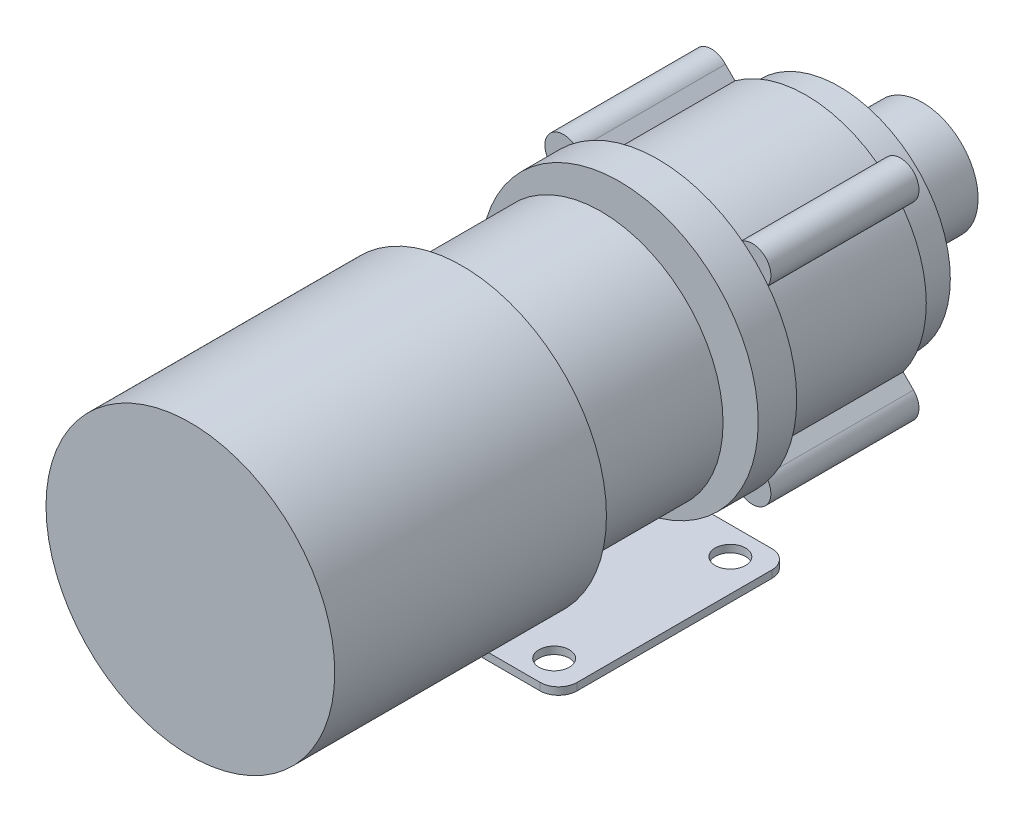
SolidWorks part; units mm, degrees
ref_plane "Front Plane" through (0, 0, 0) normal (0, 0, 1) x (1, 0, 0)
ref_plane "Top Plane" through (0, 0, 0) normal (0, 1, 0) x (1, 0, 0)
ref_plane "Right Plane" through (0, 0, 0) normal (1, 0, 0) x (0, 0, -1)
sketch "Sketch1" plane through (0, 0, 0) normal (0, 1, 0) x (1, 0, 0)
  line L0 (0, 0) -> (0, -251.206)
  line L1 (0, -251.206) -> (49.53, -251.206)
  line L2 (49.53, -251.206) -> (49.53, -157.988)
  line L3 (49.53, -157.988) -> (41.91, -157.988)
  line L4 (41.91, -157.988) -> (41.91, -110.363)
  line L5 (41.91, -110.363) -> (12.7, -110.363)
  line L6 (12.7, -110.363) -> (12.7, -104.013)
  line L7 (12.7, -104.013) -> (47.625, -104.013)
  line L8 (47.625, -104.013) -> (47.625, -90.805)
  line L9 (47.625, -90.805) -> (41.275, -90.805)
  line L10 (41.275, -90.805) -> (41.275, -40.005)
  line L11 (41.275, -40.005) -> (38.1, -40.005)
  line L12 (38.1, -40.005) -> (38.1, -28.575)
  line L13 (38.1, -28.575) -> (19.05, -28.575)
  line L14 (19.05, -28.575) -> (19.05, 0)
  line L15 (19.05, 0) -> (0, 0)
  point P15 (0, 0)
  point P19 (0, 0)
  point P20 (1.1967, 0)
  dimension "D1" = 93.218
  dimension "D2" = 47.625
  dimension "D3" = 6.35
  dimension "D4" = 13.208
  dimension "D5" = 50.8
  dimension "D6" = 11.43
  dimension "D7" = 28.575
  dimension "D8" = 49.53
  dimension "D9" = 41.91
  dimension "D10" = 12.7
  dimension "D11" = 47.625
  dimension "D12" = 41.275
  dimension "D13" = 38.1
  dimension "D14" = 19.05
revolve "Revolve1" add sketch "Sketch1" angle 360 about L0
sketch "Sketch2" plane through (0, 0, 40.005) normal (0, 0, -1) x (-1, 0, 0)
  line L0 (-27.9286, 36.9089) -> (-23.4385, 32.4187) construction
  line L1 (-24.3482, 33.3285) -> (-27.9286, 36.9089)
  line L2 (33.3285, 24.3482) -> (36.9089, 27.9286)
  line L3 (-32.4187, 32.4187) -> (-23.4385, 32.4187) construction
  line L4 (27.6284, 36.5871) -> (24.3482, 33.3285)
  line L5 (36.9089, 27.9286) -> (32.4187, 23.4385) construction
  line L6 (-32.4187, 32.4187) -> (-29.1858, 29.1858) construction
  line L7 (-36.9089, 27.9286) -> (-32.4187, 23.4385) construction
  line L8 (32.4187, 32.4187) -> (32.4187, 23.4385) construction
  line L9 (32.4187, 32.4187) -> (29.1858, 29.1858) construction
  line L10 (27.9286, 36.9089) -> (23.4385, 32.4187) construction
  line L11 (-36.5871, 27.6284) -> (-33.3285, 24.3482)
  line L12 (23.4385, 32.4187) -> (32.4187, 32.4187) construction
  line L13 (24.3482, -33.3285) -> (27.9286, -36.9089)
  line L14 (36.5871, -27.6284) -> (33.3285, -24.3482)
  line L15 (27.9286, -36.9089) -> (23.4385, -32.4187) construction
  line L16 (32.4187, -32.4187) -> (23.4385, -32.4187) construction
  line L17 (32.4187, -32.4187) -> (29.1858, -29.1858) construction
  line L18 (36.9089, -27.9286) -> (32.4187, -23.4385) construction
  line L19 (32.4187, -23.4385) -> (32.4187, -32.4187) construction
  line L20 (-33.3285, -24.3482) -> (-36.9089, -27.9286)
  line L21 (-32.4187, 23.4385) -> (-32.4187, 32.4187) construction
  line L22 (-27.6284, -36.5871) -> (-24.3482, -33.3285)
  line L23 (-36.9089, -27.9286) -> (-32.4187, -23.4385) construction
  line L24 (-32.4187, -32.4187) -> (-32.4187, -23.4385) construction
  line L25 (-32.4187, -32.4187) -> (-29.1858, -29.1858) construction
  line L26 (-27.9286, -36.9089) -> (-23.4385, -32.4187) construction
  line L27 (-23.4385, -32.4187) -> (-32.4187, -32.4187) construction
  arc A0 (-27.6161, 36.5964) -> (-36.5964, 27.6161) centre (0, 0) ccw construction
  arc A1 (-27.9286, 36.9089) -> (-36.5871, 27.6284) centre (-32.4187, 32.4187) ccw
  circle A2 centre (0, 0) radius 38.1 construction
  arc A3 (36.9089, 27.9286) -> (27.6284, 36.5871) centre (32.4187, 32.4187) ccw
  arc A4 (33.3285, 24.3482) -> (24.3482, 33.3285) centre (0, 0) ccw
  arc A5 (-24.3482, 33.3285) -> (-33.3285, 24.3482) centre (0, 0) ccw
  arc A6 (36.5964, 27.6161) -> (27.6161, 36.5964) centre (0, 0) ccw construction
  arc A7 (27.9286, -36.9089) -> (36.5871, -27.6284) centre (32.4187, -32.4187) ccw
  arc A8 (24.3482, -33.3285) -> (33.3285, -24.3482) centre (0, 0) ccw
  arc A9 (27.6161, -36.5964) -> (36.5964, -27.6161) centre (0, 0) ccw construction
  arc A10 (-36.9089, -27.9286) -> (-27.6284, -36.5871) centre (-32.4187, -32.4187) ccw
  arc A11 (-33.3285, -24.3482) -> (-24.3482, -33.3285) centre (0, 0) ccw
  arc A12 (-36.5964, -27.6161) -> (-27.6161, -36.5964) centre (0, 0) ccw construction
  point P50 (0, 0)
  dimension "D1" = 45.847
  dimension "D2" = 12.7
  dimension "D3" = 41.275
  dimension "D4" = 4
extrude "Boss-Extrude1" add sketch "Sketch2" against normal blind 50.8 separate body
ref_plane "Plane2" [suppressed] through (0, 0, 133.35) normal (0, 0, 1) x (1, 0, 0)
sketch "Sketch3" [suppressed] plane through (0, 0, 251.206) normal (0, 0, 1) x (1, 0, 0)
  line L0 (0, 0) -> (-14.9938, -25.97)
  line L1 (0, 0) -> (14.9938, -25.97)
  line L2 (0, 0) -> (0, -29.9876) construction
  line L3 (2.8571, 2.4086) -> (-13.8805, -26.5817)
  line L4 (13.8805, -26.5817) -> (-3.5159, 3.5497)
  circle A0 centre (0, 0) radius 29.9876
  circle A1 centre (0, 0) radius 28.7176
  dimension "D1" = 1.27
  dimension "D5" = 1.27
  dimension "D2" = 30
  dimension "D3" = 30
  dimension "D6" = 1.27
ref_plane "Plane3" through (0, -49.53, 0) normal (0, -1, 0) x (-1, 0, 0)
sketch "Sketch4" plane through (0, -49.53, 0) normal (0, -1, 0) x (-1, 0, 0)
  line L0 (0, -157.988) -> (0, -251.206) construction
  line L1 (49.53, -157.988) -> (-49.53, -157.988) construction
  line L2 (-49.53, -251.206) -> (49.53, -251.206) construction
  line L4 (-38.1, -169.3256) -> (38.1, -169.3256)
  line L5 (-44.45, -162.9756) -> (-44.45, -96.1736)
  line L6 (-38.1, -89.8236) -> (38.1, -89.8236)
  line L7 (44.45, -162.9756) -> (44.45, -96.1736)
  line L8 (-44.45, -169.3256) -> (44.45, -89.8236) construction
  line L9 (-44.45, -89.8236) -> (44.45, -169.3256) construction
  arc A0 (38.1, -169.3256) -> (44.45, -162.9756) centre (38.1, -162.9756) ccw
  arc A1 (-38.1, -169.3256) -> (-44.45, -162.9756) centre (-38.1, -162.9756) cw
  arc A2 (-44.45, -96.1736) -> (-38.1, -89.8236) centre (-38.1, -96.1736) cw
  arc A3 (38.1, -89.8236) -> (44.45, -96.1736) centre (38.1, -96.1736) cw
  point P6 (0, -129.5746)
  point P11 (0, -129.5746)
  dimension "D3" = 6.35
  dimension "D1" = 79.502
  dimension "D2" = 88.9
extrude "Boss-Extrude2" add sketch "Sketch4" along normal blind 2.54 separate body
sketch "Sketch5" plane through (0, -52.07, 0) normal (0, -1, 0) x (1, 0, 0)
  line L0 (44.45, 129.5746) -> (-44.45, 129.5746) construction
  line L1 (44.45, 96.1736) -> (44.45, 162.9756) construction
  line L2 (-44.45, 162.9756) -> (-44.45, 96.1736) construction
  line L4 (33.401, 159.8006) -> (-33.401, 159.8006) construction
  line L5 (33.401, 159.8006) -> (33.401, 99.3486) construction
  line L6 (33.401, 99.3486) -> (-33.401, 99.3486) construction
  line L7 (-33.401, 159.8006) -> (-33.401, 99.3486) construction
  line L8 (33.401, 159.8006) -> (-33.401, 99.3486) construction
  line L9 (33.401, 99.3486) -> (-33.401, 159.8006) construction
  circle A0 centre (33.401, 159.8006) radius 5.207
  circle A1 centre (33.401, 99.3486) radius 5.207
  circle A2 centre (-33.401, 159.8006) radius 5.207
  circle A3 centre (-33.401, 99.3486) radius 5.207
  point P6 (0, 129.5746)
  dimension "D3" = 10.414
  dimension "D1" = 66.802
  dimension "D2" = 60.452
extrude "Cut-Extrude1" cut sketch "Sketch5" against normal up to next (2.54 mm away)
